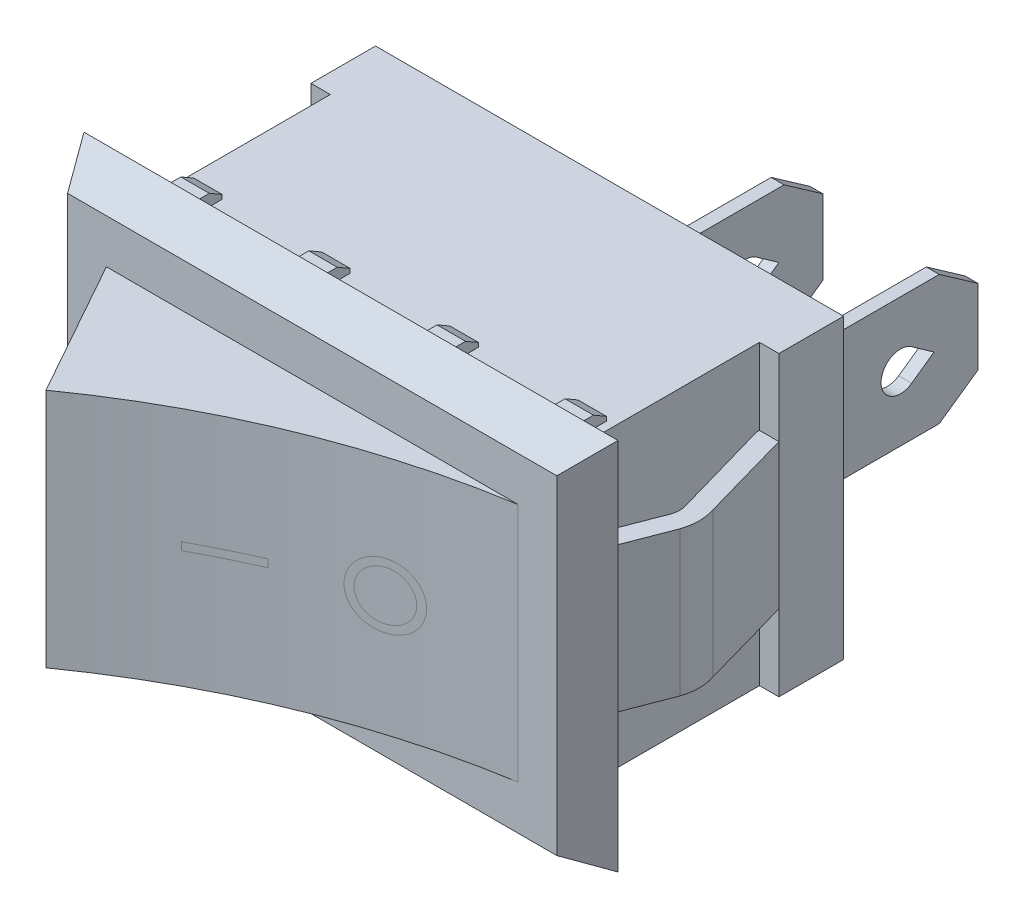
SolidWorks part; units mm, degrees
ref_plane "Front Plane" through (0, 0, 0) normal (0, 0, 1) x (1, 0, 0)
ref_plane "Top Plane" through (0, 0, 0) normal (0, 1, 0) x (1, 0, 0)
ref_plane "Right Plane" through (0, 0, 0) normal (1, 0, 0) x (0, 0, -1)
sketch "Sketch1" plane through (0, 0, 0) normal (0, 0, 1) x (1, 0, 0)
  line L0 (-8.3, 5.75) -> (8.3, -5.75) construction
  line L1 (-8.3, 5.75) -> (8.3, 5.75)
  line L2 (-8.3, 5.75) -> (-8.3, -5.75)
  line L3 (-8.3, -5.75) -> (8.3, -5.75)
  line L4 (8.3, 5.75) -> (8.3, -5.75)
  line L5 (8.3, 5.75) -> (-8.3, -5.75) construction
  point P4 (0, 0)
  dimension "D1" = 11.5
  dimension "D2" = 16.6
extrude "Boss-Extrude1" add sketch "Sketch1" along normal blind 10
sketch "Sketch2" plane through (0, 0, 10) normal (0, 0, 1) x (1, 0, 0)
  line L0 (-10.5, 7.4) -> (10.5, -7.4) construction
  line L1 (-10.5, 7.4) -> (10.5, 7.4)
  line L2 (-10.5, 7.4) -> (-10.5, -7.4)
  line L3 (-10.5, -7.4) -> (10.5, -7.4)
  line L4 (10.5, 7.4) -> (10.5, -7.4)
  line L5 (10.5, 7.4) -> (-10.5, -7.4) construction
  point P4 (0, 0)
  dimension "D1" = 21
  dimension "D2" = 14.8
extrude "Boss-Extrude2" add sketch "Sketch2" along normal blind 1.5
sketch "Sketch3" plane through (0, 0, 0) normal (0, 0, -1) x (-1, 0, 0)
  line L0 (0, 5.75) -> (0, -5.75) construction
  line L1 (-8.3, 5.75) -> (8.3, 5.75) construction
  line L2 (8.3, -5.75) -> (-8.3, -5.75) construction
  line L3 (-8.3, 0) -> (8.3, 0) construction
  line L4 (-8.3, -5.75) -> (-8.3, 5.75) construction
  line L5 (8.3, 5.75) -> (8.3, -5.75) construction
  line L6 (-0.25, 2.5) -> (0.25, -2.5) construction
  line L7 (-0.25, 2.5) -> (0.25, 2.5)
  line L8 (-0.25, 2.5) -> (-0.25, -2.5)
  line L9 (-0.25, -2.5) -> (0.25, -2.5)
  line L10 (0.25, 2.5) -> (0.25, -2.5)
  line L11 (0.25, 2.5) -> (-0.25, -2.5) construction
  line L12 (-6, 4.4419) -> (-6, -4.1746) construction
  line L13 (-6.25, 2.5) -> (-5.75, -2.5) construction
  line L14 (-6.25, 2.5) -> (-5.75, 2.5)
  line L15 (-6.25, 2.5) -> (-6.25, -2.5)
  line L16 (-6.25, -2.5) -> (-5.75, -2.5)
  line L17 (-5.75, 2.5) -> (-5.75, -2.5)
  line L18 (-5.75, 2.5) -> (-6.25, -2.5) construction
  point P16 (0, 0)
  point P24 (-6, 0)
  dimension "D1" = 0.5
  dimension "D2" = 5
  dimension "D3" = 6
  dimension "D4" = 0.5
  dimension "D5" = 5
extrude "Boss-Extrude3" add sketch "Sketch3" along normal blind 8
sketch "Sketch4" plane through (6.25, 0, 0) normal (1, 0, 0) x (0, 0, -1)
  line L0 (0, 0) -> (8, 0) construction
  line L1 (8, 2.5) -> (8, 1.4497)
  line L2 (0, 2.5) -> (0, -2.5)
  line L3 (0, -2.5) -> (8, -2.5)
  line L4 (8, 2.5) -> (8, -2.5)
  line L5 (2, 2.5) -> (2, 2.1)
  line L6 (2, 2.1) -> (2.5, 2.1)
  line L7 (2.5, 2.1) -> (2.5, 2.5)
  line L8 (2.5, 2.5) -> (2, 2.5)
  line L9 (8, 2.5) -> (6.5, 2.5)
  line L10 (6.5, 2.5) -> (8, 1.4497)
  line L11 (8, 1.4497) -> (8, 2.5)
  line L12 (6.3, 0) -> (5.4327, 0.6126)
  line L13 (2, 2.5) -> (2.5, 2.5)
  line L14 (6.5, 2.5) -> (8, 2.5)
  line L15 (2.5, -2.1) -> (2.5, -2.5)
  line L16 (2, -2.1) -> (2.5, -2.1)
  line L17 (2.5, -2.5) -> (2, -2.5)
  line L18 (2, -2.5) -> (2, -2.1)
  line L19 (6.3, 0) -> (5.4327, -0.6126)
  line L20 (6.5, -2.5) -> (8, -1.4497)
  line L21 (8, -2.5) -> (6.5, -2.5)
  line L22 (8, -2.5) -> (8, -1.4497)
  arc A0 (0, -0.75) -> (0, 0.75) centre (0, 0) ccw
  arc A1 (5.4327, 0.6126) -> (5.4327, -0.6126) centre (5, 0) ccw
  line M13 (0, 2.5) -> (0, -2.5)
  line M14 (0, -2.5) -> (8, -2.5)
  line M15 (8, -2.5) -> (8, 2.5)
  line M16 (8, 2.5) -> (0, 2.5)
  dimension "D7" = 1.5
  dimension "D8" = 1.5
  dimension "D1" = 0.5
  dimension "D2" = 0.4
  dimension "D3" = 2
  dimension "D4" = 1.5
  dimension "D5" = 35
  dimension "D6" = 5
  dimension "D9" = 1.3
extrude "Cut-Extrude1" cut sketch "Sketch4" against normal through all contours L10 M16 M15 | L20 M14 M15 | L18 L3 L15 L16 | L0 A0 M13 | L2 L0 A0 | L6 L7 L5 M16 | A1 L0 L12 | L0 A1 L19 region at (6.25, -0.2992, -5.1136) region at (6.25, 0.2992, -5.1136) region at (6.25, 2.1499, -7.5) region at (6.25, -2.1499, -7.5) region at (6.25, -0.3183, -0.3183) region at (6.25, 0.3183, -0.3183) region at (6.25, 2.3, -2.25) region at (6.25, -2.3, -2.25)
sketch "Sketch5" plane through (0, 0, 0) normal (0, 1, 0) x (1, 0, 0)
  line L1 (-8.3, 0) -> (-9.05, 0)
  line L2 (-8.3, 0) -> (-8.3, -2.5)
  line L3 (-8.3, -2.5) -> (-9.05, -2.5)
  line L4 (-9.05, 0) -> (-9.05, -2.5)
  dimension "D1" = 2.5
  dimension "D2" = 0.75
extrude "Boss-Extrude4" add sketch "Sketch5" along normal up to surface and the other way up to surface up to face at (0, 5.75, 5) other way up to face at (0, -5.75, 5)
mirror "Mirror1" about plane through (0, 0, 0) normal (1, 0, 0) of "Boss-Extrude4"
sketch "Sketch6" plane through (0, 0, 0) normal (0, 1, 0) x (1, 0, 0)
  line L0 (-8.3, -2.5) -> (-9.05, -2.5)
  line L1 (-9.05, -2.5) -> (-10.0568, -6.0544)
  line L2 (-8.3, -10) -> (-9.03, -10)
  line L3 (10.5, -10) -> (-10.5, -10) construction
  line L4 (-9.03, -10) -> (-10.0568, -7.3306)
  line L5 (-8.3, -2.5) -> (-8.3, -2.62)
  line L6 (-8.3, -10) -> (-8.3, -2.5) construction
  line L7 (-8.3, -2.62) -> (-9.3735, -6.3767)
  line L8 (-8.3, -10) -> (-8.3, -9.83)
  line L9 (-8.3, -9.83) -> (-9.3241, -7.168)
  line L10 (0.1887, 1.0639) -> (0.1887, -12.369) construction
  arc A0 (-9.3241, -7.168) -> (-9.3735, -6.3767) centre (-8.4325, -6.7152) cw
  arc A1 (-10.0568, -7.3306) -> (-10.0568, -6.0544) centre (-8.1613, -6.6925) cw
  point P18 (-8.8121, -8.499)
  point P19 (-9.5434, -8.6653)
  point P20 (-9.5534, -4.2772)
  point P22 (-8.8367, -4.4983)
  point P27 (-10.1613, -6.6925)
  dimension "D1" = 0.12
  dimension "D3" = 0.73
  dimension "D4" = 1
  dimension "D5" = 2
  dimension "D8" = 10.35
  dimension "D2" = 0.17
  dimension "D6" = 0.75
  dimension "D7" = 0.75
extrude "Boss-Extrude5" add sketch "Sketch6" along normal blind 2.8 and the other way blind 2.8
mirror "Mirror2" about plane through (0, 0, 0) normal (1, 0, 0) of "Boss-Extrude5"
chamfer "Chamfer1" distance 1.8 angle 30 4 edges at (0, 7.4, 11.5) (-10.5, 0, 11.5) (10.5, 0, 11.5) (0, -7.4, 11.5) first distance on face at (0, 7.4, 10.75) first distance on face at (-10.5, 0, 10.75) first distance on face at (10.5, 0, 10.75) first distance on face at (0, -7.4, 10.75)
sketch "Sketch7" plane through (0, 0, 0) normal (0, 1, 0) x (1, 0, 0)
  line L0 (-7.9608, -11.5) -> (7.9608, -11.5)
  line L1 (-9.4608, -11.5) -> (9.4608, -11.5) construction
  line L2 (-7.9608, -11.5) -> (-4.9952, -16.8)
  line L3 (-9.05, 0) -> (9.05, 0) construction
  arc A0 (-4.9952, -16.8) -> (7.9608, -11.5) centre (12.8472, -41.9307) cw
  point P6 (0, 0)
  point P9 (0, 0)
  point P10 (0, 0)
  point P11 (0, 0)
  point P12 (0, 0)
  point P13 (0, 0)
  point P16 (0, 0)
  dimension "D4" = 30.8205
  dimension "D1" = 16.8
extrude "Boss-Extrude6" add sketch "Sketch7" along normal mid plane 9.3
sketch "Sketch8" plane through (0, 0, 10) normal (0, 0, -1) x (-1, 0, 0)
  line L0 (0, 6.5024) -> (0, -6.4194) construction
  line L1 (-9.3219, 0) -> (9.5967, 0) construction
  line L2 (-9.05, 5.75) -> (9.05, 5.75) construction
  line L3 (-1.93, 5.75) -> (-3.03, 5.75)
  line L4 (-1.93, 5.75) -> (-1.93, 6.2)
  line L5 (-1.93, 6.2) -> (-3.03, 6.2)
  line L6 (-3.03, 5.75) -> (-3.03, 6.2)
  line L7 (-1.93, -5.75) -> (-3.03, -5.75)
  line L8 (-6.88, 5.75) -> (-7.98, 5.75)
  line L9 (-6.88, 5.75) -> (-6.88, 6.2)
  line L10 (-6.88, 6.2) -> (-7.98, 6.2)
  line L11 (-7.98, 5.75) -> (-7.98, 6.2)
  line L12 (-1.93, -5.75) -> (-1.93, -6.2)
  line L13 (-1.93, -6.2) -> (-3.03, -6.2)
  line L14 (-3.03, -5.75) -> (-3.03, -6.2)
  line L15 (-6.88, -5.75) -> (-7.98, -5.75)
  line L16 (-6.88, -5.75) -> (-6.88, -6.2)
  line L17 (-6.88, -6.2) -> (-7.98, -6.2)
  line L18 (-7.98, -5.75) -> (-7.98, -6.2)
  line L19 (1.93, -5.75) -> (1.93, -6.2)
  line L20 (1.93, -5.75) -> (3.03, -5.75)
  line L21 (3.03, -5.75) -> (3.03, -6.2)
  line L22 (1.93, -6.2) -> (3.03, -6.2)
  line L23 (6.88, -5.75) -> (6.88, -6.2)
  line L24 (6.88, -5.75) -> (7.98, -5.75)
  line L25 (7.98, -5.75) -> (7.98, -6.2)
  line L26 (6.88, -6.2) -> (7.98, -6.2)
  line L27 (1.93, 5.75) -> (3.03, 5.75)
  line L28 (1.93, 5.75) -> (1.93, 6.2)
  line L29 (1.93, 6.2) -> (3.03, 6.2)
  line L30 (3.03, 5.75) -> (3.03, 6.2)
  line L31 (6.88, 5.75) -> (6.88, 6.2)
  line L32 (6.88, 5.75) -> (7.98, 5.75)
  line L33 (6.88, 6.2) -> (7.98, 6.2)
  line L34 (7.98, 5.75) -> (7.98, 6.2)
  dimension "D1" = 1.93
  dimension "D2" = 1.1
  dimension "D3" = 3.85
  dimension "D4" = 1.1
  dimension "D5" = 0.45
  dimension "D6" = 0.45
extrude "Boss-Extrude7" add sketch "Sketch8" along normal blind 1.9
chamfer "Chamfer2" distance 0.5 angle 30 8 edges at (-7.43, -6.2, 8.1) (-2.48, -6.2, 8.1) (2.48, -6.2, 8.1) (7.43, -6.2, 8.1) (-7.43, 6.2, 8.1) (-2.48, 6.2, 8.1) (2.48, 6.2, 8.1) (7.43, 6.2, 8.1) first distance on face at (-7.43, -6.2, 9.05) first distance on face at (-2.48, -6.2, 9.05) first distance on face at (2.48, -6.2, 9.05) first distance on face at (7.43, -6.2, 9.05) first distance on face at (-7.43, 6.2, 9.05) first distance on face at (-2.48, 6.2, 9.05) first distance on face at (2.48, 6.2, 9.05) first distance on face at (7.43, 6.2, 9.05)
ref_plane "Plane1" through (5.8814, 0, 10.5112) normal (0.4883, 0, 0.8727) x (0.8727, 0, -0.4883)
sketch "Sketch9" plane through (5.8814, 0, 10.5112) normal (0.4883, 0, 0.8727) x (0.8727, 0, -0.4883)
  line L0 (-12.6088, 0) -> (1.2791, 0) construction
  line L1 (11.3595, 0) -> (-11.3595, 0) construction
  line L2 (-2.7681, 0) -> (-0.2677, 0)
  line L4 (-8.7677, 0.1888) -> (-6.2677, 0.1888)
  line L5 (-8.7677, 0.1888) -> (-8.7677, -0.1112)
  line L6 (-8.7677, -0.1112) -> (-6.2677, -0.1112)
  line L7 (-6.2677, 0.1888) -> (-6.2677, -0.1112)
  circle A0 centre (-2.7681, 0) radius 1.25
  circle A1 centre (-2.7681, 0) radius 0.95
  dimension "D1" = 2.5
  dimension "D2" = 0.3
  dimension "D3" = 2.5004
  dimension "D4" = 6
  dimension "D5" = 2.5
  dimension "D6" = 0.3
split line "Split Line1"
